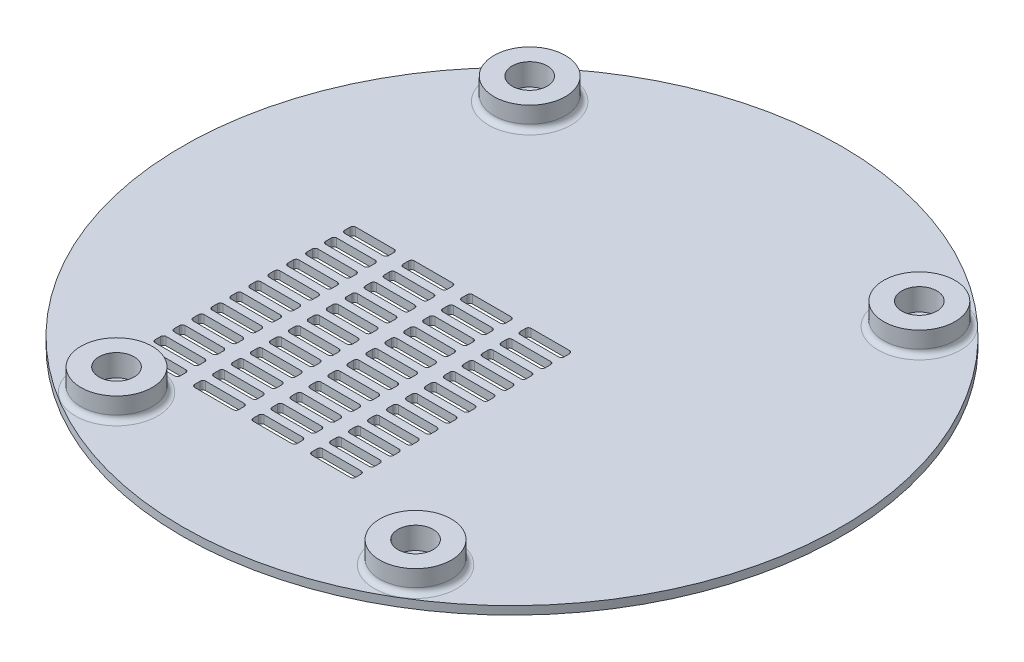
SolidWorks part; units mm, degrees
ref_plane "Спереди" through (0, 0, 0) normal (0, 0, 1) x (1, 0, 0)
ref_plane "Сверху" through (0, 0, 0) normal (0, 1, 0) x (1, 0, 0)
ref_plane "Справа" through (0, 0, 0) normal (1, 0, 0) x (0, 0, -1)
sketch "Эскиз1" plane through (0, 0, 0) normal (0, 1, 0) x (1, 0, 0)
  line L0 (0, 60) -> (0, -60) construction
  line L1 (-60, 0) -> (60, 0) construction
  circle A0 centre (0, 0) radius 60
  circle A1 centre (-35.47, 38.69) radius 1.6
  circle A2 centre (35.47, 38.69) radius 1.6
  circle A3 centre (-27.22, -44.78) radius 1.6
  circle A4 centre (27.22, -44.78) radius 1.6
  dimension "D1" = 35.47
  dimension "D3" = 120
  dimension "D4" = 3.2
  dimension "D5" = 3.2
  dimension "D2" = 38.69
  dimension "D6" = 27.22
  dimension "D7" = 44.78
extrude "Бобышка-Вытянуть1" add sketch "Эскиз1" along normal blind 1.5
chamfer "Фаска1" distance 1.6 angle 45 4 edges at (27.22, 1.5, 43.18) (35.47, 1.5, -40.29) (-35.47, 1.5, -37.09) (-27.22, 1.5, 46.38)
sketch "Эскиз2" plane through (0, 1.5, 0) normal (0, 1, 0) x (1, 0, 0)
  circle A0 centre (-35.47, 38.69) radius 6.5
  circle A1 centre (-35.47, 38.69) radius 3.2
  circle A2 centre (35.47, 38.69) radius 3.2
  circle A3 centre (35.47, 38.69) radius 6.5
  circle A4 centre (27.22, -44.78) radius 3.2
  circle A5 centre (27.22, -44.78) radius 6.5
  circle A6 centre (-27.22, -44.78) radius 3.2
  circle A7 centre (-27.22, -44.78) radius 6.5
  dimension "D1" = 13
  dimension "D2" = 13
  dimension "D3" = 13
  dimension "D4" = 13
extrude "Бобышка-Вытянуть2" add sketch "Эскиз2" along normal blind 4
fillet "Скругление1" radius 1 4 edges at (-35.47, 1.5, -32.19) (35.47, 1.5, -32.19) (27.22, 1.5, 51.28) (-27.22, 1.5, 51.28)
sketch "Эскиз3" plane through (0, 1.5, 0) normal (0, 1, 0) x (1, 0, 0)
  line L0 (0, 60) -> (0, -60) construction
  line L1 (-60, 0) -> (60, 0) construction
  line L2 (-20.85, 3.04) -> (-13.85, 3.04)
  line L3 (-32, 3.04) -> (8, 3.04) construction
  line L4 (-32, 3.04) -> (-32, -36.96) construction
  line L5 (-32, -36.96) -> (8, -36.96) construction
  line L7 (-32, 3.04) -> (8, -36.96) construction
  line L8 (-32, -36.96) -> (8, 3.04) construction
  line L9 (-32, -16.96) -> (8, -16.96) construction
  line L11 (-31.5, 3.04) -> (-24.5, 3.04)
  line L12 (-32, 2.54) -> (-32, 1.54)
  line L13 (-31.5, 1.04) -> (-24.5, 1.04)
  line L14 (-24, 2.54) -> (-24, 1.54)
  line L154 (-21.35, 2.54) -> (-21.35, 1.54)
  line L155 (-20.85, 1.04) -> (-13.85, 1.04)
  line L156 (-13.35, 2.54) -> (-13.35, 1.54)
  line L157 (-10.2, 3.04) -> (-3.2, 3.04)
  line L158 (-10.7, 2.54) -> (-10.7, 1.54)
  line L159 (-10.2, 1.04) -> (-3.2, 1.04)
  line L160 (-2.7, 2.54) -> (-2.7, 1.54)
  line L161 (0.45, 3.04) -> (7.45, 3.04)
  line L162 (-0.05, 2.54) -> (-0.05, 1.54)
  line L163 (0.45, 1.04) -> (7.45, 1.04)
  line L164 (7.95, 2.54) -> (7.95, 1.54)
  line L165 (-20.85, -0.41) -> (-13.85, -0.41)
  line L166 (-21.35, -0.91) -> (-21.35, -1.91)
  line L167 (-20.85, -2.41) -> (-13.85, -2.41)
  line L168 (-13.35, -0.91) -> (-13.35, -1.91)
  line L169 (-10.2, -0.41) -> (-3.2, -0.41)
  line L170 (-10.7, -0.91) -> (-10.7, -1.91)
  line L171 (-10.2, -2.41) -> (-3.2, -2.41)
  line L172 (-2.7, -0.91) -> (-2.7, -1.91)
  line L173 (0.45, -0.41) -> (7.45, -0.41)
  line L174 (-0.05, -0.91) -> (-0.05, -1.91)
  line L175 (0.45, -2.41) -> (7.45, -2.41)
  line L176 (7.95, -0.91) -> (7.95, -1.91)
  line L177 (-20.85, -3.86) -> (-13.85, -3.86)
  line L178 (-21.35, -4.36) -> (-21.35, -5.36)
  line L179 (-20.85, -5.86) -> (-13.85, -5.86)
  line L180 (-13.35, -4.36) -> (-13.35, -5.36)
  line L181 (-10.2, -3.86) -> (-3.2, -3.86)
  line L182 (-10.7, -4.36) -> (-10.7, -5.36)
  line L183 (-10.2, -5.86) -> (-3.2, -5.86)
  line L184 (-2.7, -4.36) -> (-2.7, -5.36)
  line L185 (0.45, -3.86) -> (7.45, -3.86)
  line L186 (-0.05, -4.36) -> (-0.05, -5.36)
  line L187 (0.45, -5.86) -> (7.45, -5.86)
  line L188 (7.95, -4.36) -> (7.95, -5.36)
  line L189 (-20.85, -7.31) -> (-13.85, -7.31)
  line L190 (-21.35, -7.81) -> (-21.35, -8.81)
  line L191 (-20.85, -9.31) -> (-13.85, -9.31)
  line L192 (-13.35, -7.81) -> (-13.35, -8.81)
  line L193 (-10.2, -7.31) -> (-3.2, -7.31)
  line L194 (-10.7, -7.81) -> (-10.7, -8.81)
  line L195 (-10.2, -9.31) -> (-3.2, -9.31)
  line L196 (-2.7, -7.81) -> (-2.7, -8.81)
  line L197 (0.45, -7.31) -> (7.45, -7.31)
  line L198 (-0.05, -7.81) -> (-0.05, -8.81)
  line L199 (0.45, -9.31) -> (7.45, -9.31)
  line L200 (7.95, -7.81) -> (7.95, -8.81)
  line L201 (-20.85, -10.76) -> (-13.85, -10.76)
  line L202 (-21.35, -11.26) -> (-21.35, -12.26)
  line L203 (-20.85, -12.76) -> (-13.85, -12.76)
  line L204 (-13.35, -11.26) -> (-13.35, -12.26)
  line L205 (-10.2, -10.76) -> (-3.2, -10.76)
  line L206 (-10.7, -11.26) -> (-10.7, -12.26)
  line L207 (-10.2, -12.76) -> (-3.2, -12.76)
  line L208 (-2.7, -11.26) -> (-2.7, -12.26)
  line L209 (0.45, -10.76) -> (7.45, -10.76)
  line L210 (-0.05, -11.26) -> (-0.05, -12.26)
  line L211 (0.45, -12.76) -> (7.45, -12.76)
  line L212 (7.95, -11.26) -> (7.95, -12.26)
  line L213 (-20.85, -14.21) -> (-13.85, -14.21)
  line L214 (-21.35, -14.71) -> (-21.35, -15.71)
  line L215 (-20.85, -16.21) -> (-13.85, -16.21)
  line L216 (-13.35, -14.71) -> (-13.35, -15.71)
  line L217 (-10.2, -14.21) -> (-3.2, -14.21)
  line L218 (-10.7, -14.71) -> (-10.7, -15.71)
  line L219 (-10.2, -16.21) -> (-3.2, -16.21)
  line L220 (-2.7, -14.71) -> (-2.7, -15.71)
  line L221 (0.45, -14.21) -> (7.45, -14.21)
  line L222 (-0.05, -14.71) -> (-0.05, -15.71)
  line L223 (0.45, -16.21) -> (7.45, -16.21)
  line L224 (7.95, -14.71) -> (7.95, -15.71)
  line L225 (-20.85, -17.66) -> (-13.85, -17.66)
  line L226 (-21.35, -18.16) -> (-21.35, -19.16)
  line L227 (-20.85, -19.66) -> (-13.85, -19.66)
  line L228 (-13.35, -18.16) -> (-13.35, -19.16)
  line L229 (-10.2, -17.66) -> (-3.2, -17.66)
  line L230 (-10.7, -18.16) -> (-10.7, -19.16)
  line L231 (-10.2, -19.66) -> (-3.2, -19.66)
  line L232 (-2.7, -18.16) -> (-2.7, -19.16)
  line L233 (0.45, -17.66) -> (7.45, -17.66)
  line L234 (-0.05, -18.16) -> (-0.05, -19.16)
  line L235 (0.45, -19.66) -> (7.45, -19.66)
  line L236 (7.95, -18.16) -> (7.95, -19.16)
  line L237 (-20.85, -21.11) -> (-13.85, -21.11)
  line L238 (-21.35, -21.61) -> (-21.35, -22.61)
  line L239 (-20.85, -23.11) -> (-13.85, -23.11)
  line L240 (-13.35, -21.61) -> (-13.35, -22.61)
  line L241 (-10.2, -21.11) -> (-3.2, -21.11)
  line L242 (-10.7, -21.61) -> (-10.7, -22.61)
  line L243 (-10.2, -23.11) -> (-3.2, -23.11)
  line L244 (-2.7, -21.61) -> (-2.7, -22.61)
  line L245 (0.45, -21.11) -> (7.45, -21.11)
  line L246 (-0.05, -21.61) -> (-0.05, -22.61)
  line L247 (0.45, -23.11) -> (7.45, -23.11)
  line L248 (7.95, -21.61) -> (7.95, -22.61)
  line L249 (-20.85, -24.56) -> (-13.85, -24.56)
  line L250 (-21.35, -25.06) -> (-21.35, -26.06)
  line L251 (-20.85, -26.56) -> (-13.85, -26.56)
  line L252 (-13.35, -25.06) -> (-13.35, -26.06)
  line L253 (-10.2, -24.56) -> (-3.2, -24.56)
  line L254 (-10.7, -25.06) -> (-10.7, -26.06)
  line L255 (-10.2, -26.56) -> (-3.2, -26.56)
  line L256 (-2.7, -25.06) -> (-2.7, -26.06)
  line L257 (0.45, -24.56) -> (7.45, -24.56)
  line L258 (-0.05, -25.06) -> (-0.05, -26.06)
  line L259 (0.45, -26.56) -> (7.45, -26.56)
  line L260 (7.95, -25.06) -> (7.95, -26.06)
  line L261 (-20.85, -28.01) -> (-13.85, -28.01)
  line L262 (-21.35, -28.51) -> (-21.35, -29.51)
  line L263 (-20.85, -30.01) -> (-13.85, -30.01)
  line L264 (-13.35, -28.51) -> (-13.35, -29.51)
  line L265 (-10.2, -28.01) -> (-3.2, -28.01)
  line L266 (-10.7, -28.51) -> (-10.7, -29.51)
  line L267 (-10.2, -30.01) -> (-3.2, -30.01)
  line L268 (-2.7, -28.51) -> (-2.7, -29.51)
  line L269 (0.45, -28.01) -> (7.45, -28.01)
  line L270 (-0.05, -28.51) -> (-0.05, -29.51)
  line L271 (0.45, -30.01) -> (7.45, -30.01)
  line L272 (7.95, -28.51) -> (7.95, -29.51)
  line L273 (-20.85, -31.46) -> (-13.85, -31.46)
  line L274 (-21.35, -31.96) -> (-21.35, -32.96)
  line L275 (-20.85, -33.46) -> (-13.85, -33.46)
  line L276 (-13.35, -31.96) -> (-13.35, -32.96)
  line L277 (-10.2, -31.46) -> (-3.2, -31.46)
  line L278 (-10.7, -31.96) -> (-10.7, -32.96)
  line L279 (-10.2, -33.46) -> (-3.2, -33.46)
  line L280 (-2.7, -31.96) -> (-2.7, -32.96)
  line L281 (0.45, -31.46) -> (7.45, -31.46)
  line L282 (-0.05, -31.96) -> (-0.05, -32.96)
  line L283 (0.45, -33.46) -> (7.45, -33.46)
  line L284 (7.95, -31.96) -> (7.95, -32.96)
  line L285 (-20.85, -34.91) -> (-13.85, -34.91)
  line L286 (-21.35, -35.41) -> (-21.35, -36.41)
  line L287 (-20.85, -36.91) -> (-13.85, -36.91)
  line L288 (-13.35, -35.41) -> (-13.35, -36.41)
  line L289 (-10.2, -34.91) -> (-3.2, -34.91)
  line L290 (-10.7, -35.41) -> (-10.7, -36.41)
  line L291 (-10.2, -36.91) -> (-3.2, -36.91)
  line L292 (-2.7, -35.41) -> (-2.7, -36.41)
  line L293 (0.45, -34.91) -> (7.45, -34.91)
  line L294 (-0.05, -35.41) -> (-0.05, -36.41)
  line L295 (0.45, -36.91) -> (7.45, -36.91)
  line L296 (7.95, -35.41) -> (7.95, -36.41)
  line L297 (-31.5, -0.41) -> (-24.5, -0.41)
  line L298 (-32, -0.91) -> (-32, -1.91)
  line L299 (-31.5, -2.41) -> (-24.5, -2.41)
  line L300 (-24, -0.91) -> (-24, -1.91)
  line L301 (-31.5, -3.86) -> (-24.5, -3.86)
  line L302 (-32, -4.36) -> (-32, -5.36)
  line L303 (-31.5, -5.86) -> (-24.5, -5.86)
  line L304 (-24, -4.36) -> (-24, -5.36)
  line L305 (-31.5, -7.31) -> (-24.5, -7.31)
  line L306 (-32, -7.81) -> (-32, -8.81)
  line L307 (-31.5, -9.31) -> (-24.5, -9.31)
  line L308 (-24, -7.81) -> (-24, -8.81)
  line L309 (-31.5, -10.76) -> (-24.5, -10.76)
  line L310 (-32, -11.26) -> (-32, -12.26)
  line L311 (-31.5, -12.76) -> (-24.5, -12.76)
  line L312 (-24, -11.26) -> (-24, -12.26)
  line L313 (-31.5, -14.21) -> (-24.5, -14.21)
  line L314 (-32, -14.71) -> (-32, -15.71)
  line L315 (-31.5, -16.21) -> (-24.5, -16.21)
  line L316 (-24, -14.71) -> (-24, -15.71)
  line L317 (-31.5, -17.66) -> (-24.5, -17.66)
  line L318 (-32, -18.16) -> (-32, -19.16)
  line L319 (-31.5, -19.66) -> (-24.5, -19.66)
  line L320 (-24, -18.16) -> (-24, -19.16)
  line L321 (-31.5, -21.11) -> (-24.5, -21.11)
  line L322 (-32, -21.61) -> (-32, -22.61)
  line L323 (-31.5, -23.11) -> (-24.5, -23.11)
  line L324 (-24, -21.61) -> (-24, -22.61)
  line L325 (-31.5, -24.56) -> (-24.5, -24.56)
  line L326 (-32, -25.06) -> (-32, -26.06)
  line L327 (-31.5, -26.56) -> (-24.5, -26.56)
  line L328 (-24, -25.06) -> (-24, -26.06)
  line L329 (-31.5, -28.01) -> (-24.5, -28.01)
  line L330 (-32, -28.51) -> (-32, -29.51)
  line L331 (-31.5, -30.01) -> (-24.5, -30.01)
  line L332 (-24, -28.51) -> (-24, -29.51)
  line L333 (-31.5, -31.46) -> (-24.5, -31.46)
  line L334 (-32, -31.96) -> (-32, -32.96)
  line L335 (-31.5, -33.46) -> (-24.5, -33.46)
  line L336 (-24, -31.96) -> (-24, -32.96)
  line L337 (-31.5, -34.91) -> (-24.5, -34.91)
  line L338 (-32, -35.41) -> (-32, -36.41)
  line L339 (-31.5, -36.91) -> (-24.5, -36.91)
  line L340 (-24, -35.41) -> (-24, -36.41)
  circle A0 centre (0, 0) radius 60 construction
  arc A9 (-24, 1.54) -> (-24.5, 1.04) centre (-24.5, 1.54) cw
  arc A10 (-32, 1.54) -> (-31.5, 1.04) centre (-31.5, 1.54) ccw
  arc A11 (-31.5, 3.04) -> (-32, 2.54) centre (-31.5, 2.54) ccw
  arc A12 (-24.5, 3.04) -> (-24, 2.54) centre (-24.5, 2.54) cw
  arc A13 (-13.35, 1.54) -> (-13.85, 1.04) centre (-13.85, 1.54) cw
  arc A14 (-21.35, 1.54) -> (-20.85, 1.04) centre (-20.85, 1.54) ccw
  arc A15 (-20.85, 3.04) -> (-21.35, 2.54) centre (-20.85, 2.54) ccw
  arc A16 (-13.85, 3.04) -> (-13.35, 2.54) centre (-13.85, 2.54) cw
  arc A17 (-2.7, 1.54) -> (-3.2, 1.04) centre (-3.2, 1.54) cw
  arc A18 (-10.7, 1.54) -> (-10.2, 1.04) centre (-10.2, 1.54) ccw
  arc A19 (-10.2, 3.04) -> (-10.7, 2.54) centre (-10.2, 2.54) ccw
  arc A20 (-3.2, 3.04) -> (-2.7, 2.54) centre (-3.2, 2.54) cw
  arc A21 (7.95, 1.54) -> (7.45, 1.04) centre (7.45, 1.54) cw
  arc A22 (-0.05, 1.54) -> (0.45, 1.04) centre (0.45, 1.54) ccw
  arc A23 (0.45, 3.04) -> (-0.05, 2.54) centre (0.45, 2.54) ccw
  arc A24 (7.45, 3.04) -> (7.95, 2.54) centre (7.45, 2.54) cw
  arc A25 (-13.35, -1.91) -> (-13.85, -2.41) centre (-13.85, -1.91) cw
  arc A26 (-21.35, -1.91) -> (-20.85, -2.41) centre (-20.85, -1.91) ccw
  arc A27 (-20.85, -0.41) -> (-21.35, -0.91) centre (-20.85, -0.91) ccw
  arc A28 (-13.85, -0.41) -> (-13.35, -0.91) centre (-13.85, -0.91) cw
  arc A29 (-2.7, -1.91) -> (-3.2, -2.41) centre (-3.2, -1.91) cw
  arc A30 (-10.7, -1.91) -> (-10.2, -2.41) centre (-10.2, -1.91) ccw
  arc A31 (-10.2, -0.41) -> (-10.7, -0.91) centre (-10.2, -0.91) ccw
  arc A32 (-3.2, -0.41) -> (-2.7, -0.91) centre (-3.2, -0.91) cw
  arc A33 (7.95, -1.91) -> (7.45, -2.41) centre (7.45, -1.91) cw
  arc A34 (-0.05, -1.91) -> (0.45, -2.41) centre (0.45, -1.91) ccw
  arc A35 (0.45, -0.41) -> (-0.05, -0.91) centre (0.45, -0.91) ccw
  arc A36 (7.45, -0.41) -> (7.95, -0.91) centre (7.45, -0.91) cw
  arc A37 (-13.35, -5.36) -> (-13.85, -5.86) centre (-13.85, -5.36) cw
  arc A38 (-21.35, -5.36) -> (-20.85, -5.86) centre (-20.85, -5.36) ccw
  arc A39 (-20.85, -3.86) -> (-21.35, -4.36) centre (-20.85, -4.36) ccw
  arc A40 (-13.85, -3.86) -> (-13.35, -4.36) centre (-13.85, -4.36) cw
  arc A41 (-2.7, -5.36) -> (-3.2, -5.86) centre (-3.2, -5.36) cw
  arc A42 (-10.7, -5.36) -> (-10.2, -5.86) centre (-10.2, -5.36) ccw
  arc A43 (-10.2, -3.86) -> (-10.7, -4.36) centre (-10.2, -4.36) ccw
  arc A44 (-3.2, -3.86) -> (-2.7, -4.36) centre (-3.2, -4.36) cw
  arc A45 (7.95, -5.36) -> (7.45, -5.86) centre (7.45, -5.36) cw
  arc A46 (-0.05, -5.36) -> (0.45, -5.86) centre (0.45, -5.36) ccw
  arc A47 (0.45, -3.86) -> (-0.05, -4.36) centre (0.45, -4.36) ccw
  arc A48 (7.45, -3.86) -> (7.95, -4.36) centre (7.45, -4.36) cw
  arc A49 (-13.35, -8.81) -> (-13.85, -9.31) centre (-13.85, -8.81) cw
  arc A50 (-21.35, -8.81) -> (-20.85, -9.31) centre (-20.85, -8.81) ccw
  arc A51 (-20.85, -7.31) -> (-21.35, -7.81) centre (-20.85, -7.81) ccw
  arc A52 (-13.85, -7.31) -> (-13.35, -7.81) centre (-13.85, -7.81) cw
  arc A53 (-2.7, -8.81) -> (-3.2, -9.31) centre (-3.2, -8.81) cw
  arc A54 (-10.7, -8.81) -> (-10.2, -9.31) centre (-10.2, -8.81) ccw
  arc A55 (-10.2, -7.31) -> (-10.7, -7.81) centre (-10.2, -7.81) ccw
  arc A56 (-3.2, -7.31) -> (-2.7, -7.81) centre (-3.2, -7.81) cw
  arc A57 (7.95, -8.81) -> (7.45, -9.31) centre (7.45, -8.81) cw
  arc A58 (-0.05, -8.81) -> (0.45, -9.31) centre (0.45, -8.81) ccw
  arc A59 (0.45, -7.31) -> (-0.05, -7.81) centre (0.45, -7.81) ccw
  arc A60 (7.45, -7.31) -> (7.95, -7.81) centre (7.45, -7.81) cw
  arc A61 (-13.35, -12.26) -> (-13.85, -12.76) centre (-13.85, -12.26) cw
  arc A62 (-21.35, -12.26) -> (-20.85, -12.76) centre (-20.85, -12.26) ccw
  arc A63 (-20.85, -10.76) -> (-21.35, -11.26) centre (-20.85, -11.26) ccw
  arc A64 (-13.85, -10.76) -> (-13.35, -11.26) centre (-13.85, -11.26) cw
  arc A65 (-2.7, -12.26) -> (-3.2, -12.76) centre (-3.2, -12.26) cw
  arc A66 (-10.7, -12.26) -> (-10.2, -12.76) centre (-10.2, -12.26) ccw
  arc A67 (-10.2, -10.76) -> (-10.7, -11.26) centre (-10.2, -11.26) ccw
  arc A68 (-3.2, -10.76) -> (-2.7, -11.26) centre (-3.2, -11.26) cw
  arc A69 (7.95, -12.26) -> (7.45, -12.76) centre (7.45, -12.26) cw
  arc A70 (-0.05, -12.26) -> (0.45, -12.76) centre (0.45, -12.26) ccw
  arc A71 (0.45, -10.76) -> (-0.05, -11.26) centre (0.45, -11.26) ccw
  arc A72 (7.45, -10.76) -> (7.95, -11.26) centre (7.45, -11.26) cw
  arc A73 (-13.35, -15.71) -> (-13.85, -16.21) centre (-13.85, -15.71) cw
  arc A74 (-21.35, -15.71) -> (-20.85, -16.21) centre (-20.85, -15.71) ccw
  arc A75 (-20.85, -14.21) -> (-21.35, -14.71) centre (-20.85, -14.71) ccw
  arc A76 (-13.85, -14.21) -> (-13.35, -14.71) centre (-13.85, -14.71) cw
  arc A77 (-2.7, -15.71) -> (-3.2, -16.21) centre (-3.2, -15.71) cw
  arc A78 (-10.7, -15.71) -> (-10.2, -16.21) centre (-10.2, -15.71) ccw
  arc A79 (-10.2, -14.21) -> (-10.7, -14.71) centre (-10.2, -14.71) ccw
  arc A80 (-3.2, -14.21) -> (-2.7, -14.71) centre (-3.2, -14.71) cw
  arc A81 (7.95, -15.71) -> (7.45, -16.21) centre (7.45, -15.71) cw
  arc A82 (-0.05, -15.71) -> (0.45, -16.21) centre (0.45, -15.71) ccw
  arc A83 (0.45, -14.21) -> (-0.05, -14.71) centre (0.45, -14.71) ccw
  arc A84 (7.45, -14.21) -> (7.95, -14.71) centre (7.45, -14.71) cw
  arc A85 (-13.35, -19.16) -> (-13.85, -19.66) centre (-13.85, -19.16) cw
  arc A86 (-21.35, -19.16) -> (-20.85, -19.66) centre (-20.85, -19.16) ccw
  arc A87 (-20.85, -17.66) -> (-21.35, -18.16) centre (-20.85, -18.16) ccw
  arc A88 (-13.85, -17.66) -> (-13.35, -18.16) centre (-13.85, -18.16) cw
  arc A89 (-2.7, -19.16) -> (-3.2, -19.66) centre (-3.2, -19.16) cw
  arc A90 (-10.7, -19.16) -> (-10.2, -19.66) centre (-10.2, -19.16) ccw
  arc A91 (-10.2, -17.66) -> (-10.7, -18.16) centre (-10.2, -18.16) ccw
  arc A92 (-3.2, -17.66) -> (-2.7, -18.16) centre (-3.2, -18.16) cw
  arc A93 (7.95, -19.16) -> (7.45, -19.66) centre (7.45, -19.16) cw
  arc A94 (-0.05, -19.16) -> (0.45, -19.66) centre (0.45, -19.16) ccw
  arc A95 (0.45, -17.66) -> (-0.05, -18.16) centre (0.45, -18.16) ccw
  arc A96 (7.45, -17.66) -> (7.95, -18.16) centre (7.45, -18.16) cw
  arc A97 (-13.35, -22.61) -> (-13.85, -23.11) centre (-13.85, -22.61) cw
  arc A98 (-21.35, -22.61) -> (-20.85, -23.11) centre (-20.85, -22.61) ccw
  arc A99 (-20.85, -21.11) -> (-21.35, -21.61) centre (-20.85, -21.61) ccw
  arc A100 (-13.85, -21.11) -> (-13.35, -21.61) centre (-13.85, -21.61) cw
  arc A101 (-2.7, -22.61) -> (-3.2, -23.11) centre (-3.2, -22.61) cw
  arc A102 (-10.7, -22.61) -> (-10.2, -23.11) centre (-10.2, -22.61) ccw
  arc A103 (-10.2, -21.11) -> (-10.7, -21.61) centre (-10.2, -21.61) ccw
  arc A104 (-3.2, -21.11) -> (-2.7, -21.61) centre (-3.2, -21.61) cw
  arc A105 (7.95, -22.61) -> (7.45, -23.11) centre (7.45, -22.61) cw
  arc A106 (-0.05, -22.61) -> (0.45, -23.11) centre (0.45, -22.61) ccw
  arc A107 (0.45, -21.11) -> (-0.05, -21.61) centre (0.45, -21.61) ccw
  arc A108 (7.45, -21.11) -> (7.95, -21.61) centre (7.45, -21.61) cw
  arc A109 (-13.35, -26.06) -> (-13.85, -26.56) centre (-13.85, -26.06) cw
  arc A110 (-21.35, -26.06) -> (-20.85, -26.56) centre (-20.85, -26.06) ccw
  arc A111 (-20.85, -24.56) -> (-21.35, -25.06) centre (-20.85, -25.06) ccw
  arc A112 (-13.85, -24.56) -> (-13.35, -25.06) centre (-13.85, -25.06) cw
  arc A113 (-2.7, -26.06) -> (-3.2, -26.56) centre (-3.2, -26.06) cw
  arc A114 (-10.7, -26.06) -> (-10.2, -26.56) centre (-10.2, -26.06) ccw
  arc A115 (-10.2, -24.56) -> (-10.7, -25.06) centre (-10.2, -25.06) ccw
  arc A116 (-3.2, -24.56) -> (-2.7, -25.06) centre (-3.2, -25.06) cw
  arc A117 (7.95, -26.06) -> (7.45, -26.56) centre (7.45, -26.06) cw
  arc A118 (-0.05, -26.06) -> (0.45, -26.56) centre (0.45, -26.06) ccw
  arc A119 (0.45, -24.56) -> (-0.05, -25.06) centre (0.45, -25.06) ccw
  arc A120 (7.45, -24.56) -> (7.95, -25.06) centre (7.45, -25.06) cw
  arc A121 (-13.35, -29.51) -> (-13.85, -30.01) centre (-13.85, -29.51) cw
  arc A122 (-21.35, -29.51) -> (-20.85, -30.01) centre (-20.85, -29.51) ccw
  arc A123 (-20.85, -28.01) -> (-21.35, -28.51) centre (-20.85, -28.51) ccw
  arc A124 (-13.85, -28.01) -> (-13.35, -28.51) centre (-13.85, -28.51) cw
  arc A125 (-2.7, -29.51) -> (-3.2, -30.01) centre (-3.2, -29.51) cw
  arc A126 (-10.7, -29.51) -> (-10.2, -30.01) centre (-10.2, -29.51) ccw
  arc A127 (-10.2, -28.01) -> (-10.7, -28.51) centre (-10.2, -28.51) ccw
  arc A128 (-3.2, -28.01) -> (-2.7, -28.51) centre (-3.2, -28.51) cw
  arc A129 (7.95, -29.51) -> (7.45, -30.01) centre (7.45, -29.51) cw
  arc A130 (-0.05, -29.51) -> (0.45, -30.01) centre (0.45, -29.51) ccw
  arc A131 (0.45, -28.01) -> (-0.05, -28.51) centre (0.45, -28.51) ccw
  arc A132 (7.45, -28.01) -> (7.95, -28.51) centre (7.45, -28.51) cw
  arc A133 (-13.35, -32.96) -> (-13.85, -33.46) centre (-13.85, -32.96) cw
  arc A134 (-21.35, -32.96) -> (-20.85, -33.46) centre (-20.85, -32.96) ccw
  arc A135 (-20.85, -31.46) -> (-21.35, -31.96) centre (-20.85, -31.96) ccw
  arc A136 (-13.85, -31.46) -> (-13.35, -31.96) centre (-13.85, -31.96) cw
  arc A137 (-2.7, -32.96) -> (-3.2, -33.46) centre (-3.2, -32.96) cw
  arc A138 (-10.7, -32.96) -> (-10.2, -33.46) centre (-10.2, -32.96) ccw
  arc A139 (-10.2, -31.46) -> (-10.7, -31.96) centre (-10.2, -31.96) ccw
  arc A140 (-3.2, -31.46) -> (-2.7, -31.96) centre (-3.2, -31.96) cw
  arc A141 (7.95, -32.96) -> (7.45, -33.46) centre (7.45, -32.96) cw
  arc A142 (-0.05, -32.96) -> (0.45, -33.46) centre (0.45, -32.96) ccw
  arc A143 (0.45, -31.46) -> (-0.05, -31.96) centre (0.45, -31.96) ccw
  arc A144 (7.45, -31.46) -> (7.95, -31.96) centre (7.45, -31.96) cw
  arc A145 (-13.35, -36.41) -> (-13.85, -36.91) centre (-13.85, -36.41) cw
  arc A146 (-21.35, -36.41) -> (-20.85, -36.91) centre (-20.85, -36.41) ccw
  arc A147 (-20.85, -34.91) -> (-21.35, -35.41) centre (-20.85, -35.41) ccw
  arc A148 (-13.85, -34.91) -> (-13.35, -35.41) centre (-13.85, -35.41) cw
  arc A149 (-2.7, -36.41) -> (-3.2, -36.91) centre (-3.2, -36.41) cw
  arc A150 (-10.7, -36.41) -> (-10.2, -36.91) centre (-10.2, -36.41) ccw
  arc A151 (-10.2, -34.91) -> (-10.7, -35.41) centre (-10.2, -35.41) ccw
  arc A152 (-3.2, -34.91) -> (-2.7, -35.41) centre (-3.2, -35.41) cw
  arc A153 (7.95, -36.41) -> (7.45, -36.91) centre (7.45, -36.41) cw
  arc A154 (-0.05, -36.41) -> (0.45, -36.91) centre (0.45, -36.41) ccw
  arc A155 (0.45, -34.91) -> (-0.05, -35.41) centre (0.45, -35.41) ccw
  arc A156 (7.45, -34.91) -> (7.95, -35.41) centre (7.45, -35.41) cw
  arc A157 (-24, -1.91) -> (-24.5, -2.41) centre (-24.5, -1.91) cw
  arc A158 (-32, -1.91) -> (-31.5, -2.41) centre (-31.5, -1.91) ccw
  arc A159 (-31.5, -0.41) -> (-32, -0.91) centre (-31.5, -0.91) ccw
  arc A160 (-24.5, -0.41) -> (-24, -0.91) centre (-24.5, -0.91) cw
  arc A161 (-24, -5.36) -> (-24.5, -5.86) centre (-24.5, -5.36) cw
  arc A162 (-32, -5.36) -> (-31.5, -5.86) centre (-31.5, -5.36) ccw
  arc A163 (-31.5, -3.86) -> (-32, -4.36) centre (-31.5, -4.36) ccw
  arc A164 (-24.5, -3.86) -> (-24, -4.36) centre (-24.5, -4.36) cw
  arc A165 (-24, -8.81) -> (-24.5, -9.31) centre (-24.5, -8.81) cw
  arc A166 (-32, -8.81) -> (-31.5, -9.31) centre (-31.5, -8.81) ccw
  arc A167 (-31.5, -7.31) -> (-32, -7.81) centre (-31.5, -7.81) ccw
  arc A168 (-24.5, -7.31) -> (-24, -7.81) centre (-24.5, -7.81) cw
  arc A169 (-24, -12.26) -> (-24.5, -12.76) centre (-24.5, -12.26) cw
  arc A170 (-32, -12.26) -> (-31.5, -12.76) centre (-31.5, -12.26) ccw
  arc A171 (-31.5, -10.76) -> (-32, -11.26) centre (-31.5, -11.26) ccw
  arc A172 (-24.5, -10.76) -> (-24, -11.26) centre (-24.5, -11.26) cw
  arc A173 (-24, -15.71) -> (-24.5, -16.21) centre (-24.5, -15.71) cw
  arc A174 (-32, -15.71) -> (-31.5, -16.21) centre (-31.5, -15.71) ccw
  arc A175 (-31.5, -14.21) -> (-32, -14.71) centre (-31.5, -14.71) ccw
  arc A176 (-24.5, -14.21) -> (-24, -14.71) centre (-24.5, -14.71) cw
  arc A177 (-24, -19.16) -> (-24.5, -19.66) centre (-24.5, -19.16) cw
  arc A178 (-32, -19.16) -> (-31.5, -19.66) centre (-31.5, -19.16) ccw
  arc A179 (-31.5, -17.66) -> (-32, -18.16) centre (-31.5, -18.16) ccw
  arc A180 (-24.5, -17.66) -> (-24, -18.16) centre (-24.5, -18.16) cw
  arc A181 (-24, -22.61) -> (-24.5, -23.11) centre (-24.5, -22.61) cw
  arc A182 (-32, -22.61) -> (-31.5, -23.11) centre (-31.5, -22.61) ccw
  arc A183 (-31.5, -21.11) -> (-32, -21.61) centre (-31.5, -21.61) ccw
  arc A184 (-24.5, -21.11) -> (-24, -21.61) centre (-24.5, -21.61) cw
  arc A185 (-24, -26.06) -> (-24.5, -26.56) centre (-24.5, -26.06) cw
  arc A186 (-32, -26.06) -> (-31.5, -26.56) centre (-31.5, -26.06) ccw
  arc A187 (-31.5, -24.56) -> (-32, -25.06) centre (-31.5, -25.06) ccw
  arc A188 (-24.5, -24.56) -> (-24, -25.06) centre (-24.5, -25.06) cw
  arc A189 (-24, -29.51) -> (-24.5, -30.01) centre (-24.5, -29.51) cw
  arc A190 (-32, -29.51) -> (-31.5, -30.01) centre (-31.5, -29.51) ccw
  arc A191 (-31.5, -28.01) -> (-32, -28.51) centre (-31.5, -28.51) ccw
  arc A192 (-24.5, -28.01) -> (-24, -28.51) centre (-24.5, -28.51) cw
  arc A193 (-24, -32.96) -> (-24.5, -33.46) centre (-24.5, -32.96) cw
  arc A194 (-32, -32.96) -> (-31.5, -33.46) centre (-31.5, -32.96) ccw
  arc A195 (-31.5, -31.46) -> (-32, -31.96) centre (-31.5, -31.96) ccw
  arc A196 (-24.5, -31.46) -> (-24, -31.96) centre (-24.5, -31.96) cw
  arc A197 (-24, -36.41) -> (-24.5, -36.91) centre (-24.5, -36.41) cw
  arc A198 (-32, -36.41) -> (-31.5, -36.91) centre (-31.5, -36.41) ccw
  arc A199 (-31.5, -34.91) -> (-32, -35.41) centre (-31.5, -35.41) ccw
  arc A200 (-24.5, -34.91) -> (-24, -35.41) centre (-24.5, -35.41) cw
  point P162 (-24, 1.04)
  point P170 (-24, 3.04)
  dimension "D5" = 8
  dimension "D6" = 2
  dimension "D9" = 0.5
  dimension "D10" = 0.5
  dimension "D1" = 40
  dimension "D2" = 4
  dimension "D3" = 12
extrude "Вырез-Вытянуть1" cut sketch "Эскиз3" against normal through all
equation "\"D2@Эскиз2\"=\"D1@Эскиз2\""
equation "\"D3@Эскиз2\"=\"D1@Эскиз2\""
equation "\"D4@Эскиз2\"=\"D1@Эскиз2\""
